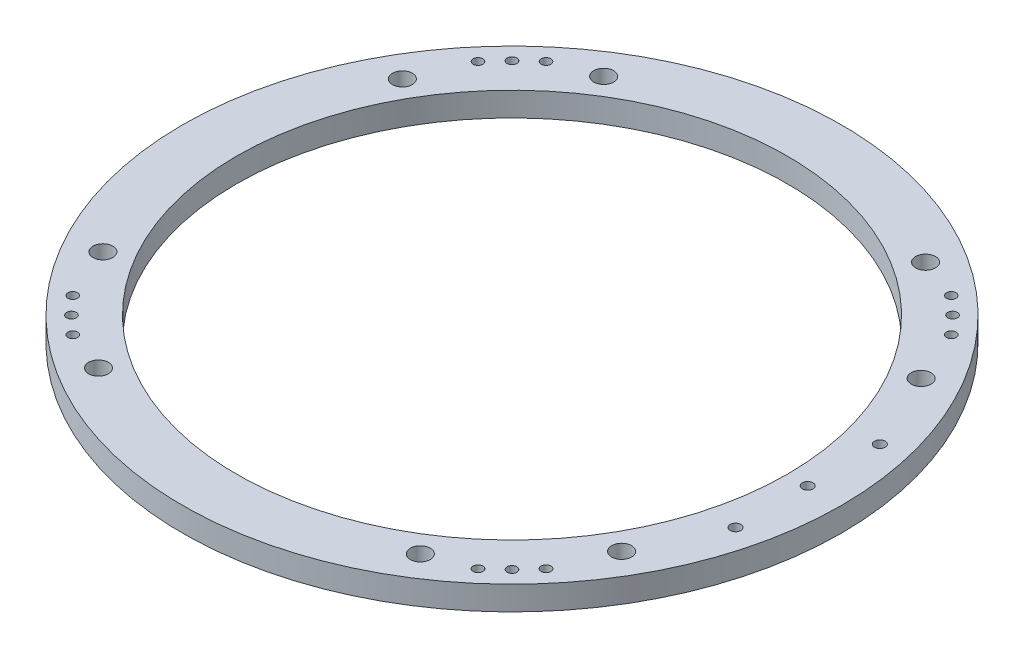
SolidWorks part; units mm, degrees
ref_plane "Front Plane" through (0, 0, 0) normal (0, 0, 1) x (1, 0, 0)
ref_plane "Top Plane" through (0, 0, 0) normal (0, 1, 0) x (1, 0, 0)
ref_plane "Right Plane" through (0, 0, 0) normal (1, 0, 0) x (0, 0, -1)
sketch "Sketch1" plane through (0, 0, 0) normal (0, 0, 1) x (1, 0, 0)
  line L0 (0, 1125.8152) -> (0, -48874.1848) construction
  line L1 (145.5262, 1052.195) -> (152.4, 1052.195)
  line L9 (145.5262, 1064.895) -> (174.1012, 1064.895)
  line L10 (145.5262, 1064.895) -> (145.5262, 1052.195)
  line L11 (145.5262, 1052.195) -> (174.1012, 1052.195)
  line L12 (174.1012, 1064.895) -> (174.1012, 1052.195)
revolve "Revolve1" add sketch "Sketch1" angle 360 about L0 region at (159.8137, 1058.545, 0)
hole_wizard "1/4-20 Tapped Hole1" positions "Sketch9" profile "Sketch10" tap size "1/4-20" standard "ANSI Inch" end condition through all
sketch "Sketch9" plane through (0, 1052.195, 0) normal (0, -1, 0) x (-1, 0, 0)
  line L0 (0, 0) -> (116.373, 116.373) construction
  line L3 (0, 0) -> (107.0457, 125.0062) construction
  arc A0 (107.0457, 125.0062) -> (125.0062, 107.0457) centre (0, 0) cw
  circle A1 centre (0, 0) radius 164.5762 construction
  point P0 (107.0457, 125.0062)
  point P2 (125.0062, 107.0457)
  point P15 (116.373, 116.373)
  point P21 (112.2532, 112.2532)
  point P22 (116.373, 116.373)
  point P24 (125.0062, 107.0457)
  point P26 (105.7876, 126.0727)
  point P29 (107.0457, 125.0062)
  point P31 (125.0062, 107.0457)
sketch "Sketch10" plane through (-107.0457, 1052.195, -125.0062) normal (1, 0, 0) x (0, 0, -1)
  line L0 (0, 0) -> (0, 12.7)
  line L1 (0, 12.7) -> (2.5527, 12.7)
  line L2 (2.5527, 12.7) -> (2.5527, 0)
  line L5 (2.5527, 0) -> (0, 0)
  line L11 (0, -6.35) -> (0, 107.95) construction
  dimension "Thru Tap Drill Dia." = 5.1054
  dimension "Thru Tap Drill Depth" = 12.7
cosmetic thread "Hole Thread1" parameters "D2"=6.35
cosmetic thread "Hole Thread2" parameters "D2"=6.35
cosmetic thread "Hole Thread3" parameters "D2"=6.35
pattern_circular "CirPattern1" count 4 over 360 about axis through (0, 1125.8152, 0) along (0, 1, 0) of "1/4-20 Tapped Hole1"
ref_plane "Plane1" through (0, 1058.545, 0) normal (0, 1, 0) x (1, 0, 0)
hole_wizard "#10 Clearance Hole1" positions "Sketch14" profile "Sketch15" hole size "#10" standard "ANSI Inch" end condition through all
sketch "Sketch14" plane through (0, 1064.895, 0) normal (0, 1, 0) x (1, 0, 0)
  point P0 (156.21, 38.1)
  point P3 (156.21, 0)
  point P6 (156.21, -38.1)
sketch "Sketch15" plane through (156.21, 1064.895, -38.1) normal (1, 0, 0) x (0, 0, 1)
  line L0 (0, 0) -> (0, 12.7)
  line L1 (0, 12.7) -> (2.8067, 12.7)
  line L2 (2.8067, 12.7) -> (2.8067, 0)
  line L5 (2.8067, 0) -> (0, 0)
  line L11 (0, -6.35) -> (0, 107.95) construction
  dimension "Thru Hole Dia." = 5.6134
  dimension "Thru Hole Depth" = 12.7
hole_wizard "Z (0.413) Diameter Hole1" positions "Sketch16" profile "Sketch17" hole size "Z" standard "ANSI Inch" end condition through all
sketch "Sketch16" plane through (0, 1064.895, 0) normal (0, 1, 0) x (1, 0, 0)
  line L0 (-137.0279, -79.1131) -> (137.0279, 79.1131) construction
  line L4 (137.0279, -79.1131) -> (-137.0279, 79.1131) construction
  line L6 (0, 0) -> (0, 158.2262) construction
  line L8 (-85.0149, -133.4467) -> (85.0149, 133.4467) construction
  line L11 (-85.0149, 133.4467) -> (85.0149, -133.4467) construction
  circle A0 centre (0, 0) radius 158.2262 construction
  circle A1 centre (0, 0) radius 145.5262 construction
  point P0 (-137.0279, -79.1131)
  point P2 (137.0279, -79.1131)
  point P4 (137.0279, 79.1131)
  point P6 (-137.0279, 79.1131)
  point P37 (-85.0149, 133.4467)
  point P39 (85.0149, 133.4467)
  point P41 (85.0149, -133.4467)
  point P43 (-85.0149, -133.4467)
  dimension "D2" = 12.7
  dimension "D1" = 120
  dimension "D3" = 65
sketch "Sketch17" plane through (-137.0279, 1064.895, 79.1131) normal (1, 0, 0) x (0, 0, 1)
  line L0 (0, 0) -> (0, 12.7)
  line L1 (0, 12.7) -> (5.2451, 12.7)
  line L2 (5.2451, 12.7) -> (5.2451, 0)
  line L5 (5.2451, 0) -> (0, 0)
  line L11 (0, -6.35) -> (0, 107.95) construction
  dimension "Thru Hole Dia." = 10.4902
  dimension "Thru Hole Depth" = 12.7
